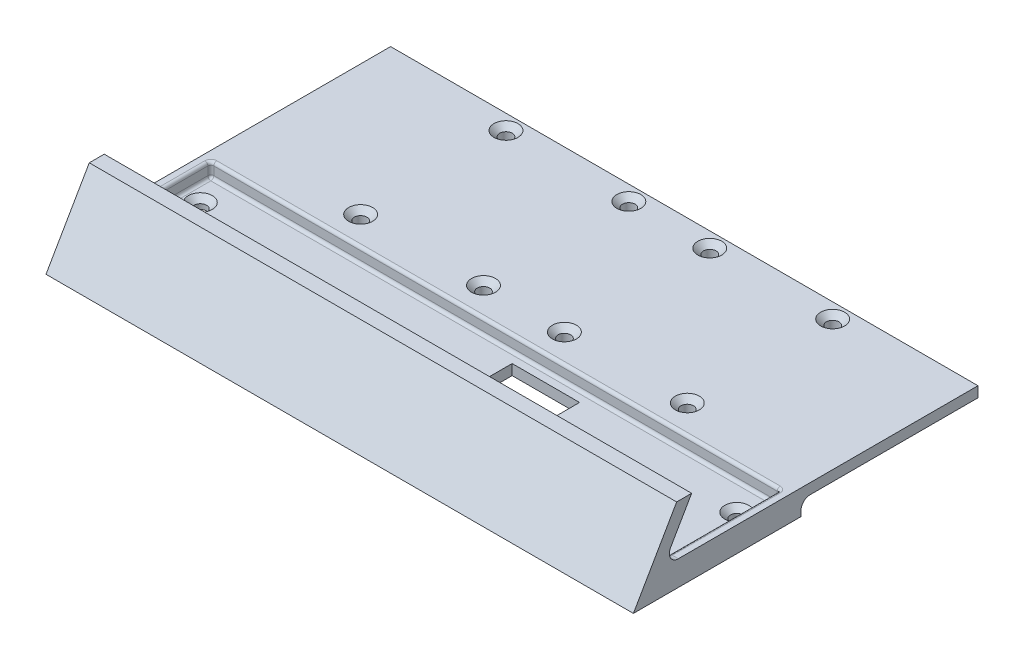
SolidWorks part; units mm, degrees
ref_plane "Alzado" through (0, 0, 0) normal (0, 0, 1) x (1, 0, 0)
ref_plane "Planta" through (0, 0, 0) normal (0, 1, 0) x (1, 0, 0)
ref_plane "Vista lateral" through (0, 0, 0) normal (1, 0, 0) x (0, 0, -1)
sketch "Sketch1" plane through (0, 0, 0) normal (1, 0, 0) x (0, 0, -1)
  line L0 (-13.9334, 0) -> (0.5004, 25)
  line L1 (-88.9489, -50.86) -> (38.0613, -50.86) construction
  line L2 (0.5004, 25) -> (5.5004, 25)
  line L3 (5.5004, 25) -> (-8.9334, 0)
  line L4 (-8.9334, 0) -> (-13.9334, 0)
  dimension "D1" = 120
  dimension "D2" = 25
  dimension "D3" = 5
  dimension "D4" = 5
extrude "Boss-Extrude1" add sketch "Sketch1" along normal blind 196
sketch "Sketch2" plane through (0, 0, 0) normal (1, 0, 0) x (0, 0, -1)
  line L0 (42.0107, 0) -> (42.0107, 4.8111)
  line L1 (101.0511, 0) -> (101.0511, -50.86) construction
  line L6 (-11.9127, 3.5) -> (-13.9334, 0)
  line L8 (-11.9127, 3.5) -> (38.0613, 3.5)
  line L9 (-13.9334, 0) -> (38.0613, 0)
  line L10 (42.0107, 4.8111) -> (101.0511, 4.8111)
  line L16 (101.0511, 4.8111) -> (101.0511, 8.3111)
  line L17 (101.0511, 8.3111) -> (38.0613, 8.3111)
  line L18 (38.0613, 8.3111) -> (38.0613, 3.5)
  line L19 (38.0613, 0) -> (42.0107, 0)
  point P9 (38.0613, 8.3111)
  point P12 (-13.9334, 0)
  point P13 (-11.9127, 3.5)
  dimension "D1" = 3.5
  dimension "D2" = 3.5
extrude "Boss-Extrude2" add sketch "Sketch2" along normal blind 196
sketch "Sketch3" plane through (0, 0, 0) normal (0, -1, 0) x (1, 0, 0)
  circle A0 centre (187.5, -29.0613) radius 1.585
  circle A1 centre (8.5, -29.0613) radius 1.585
  circle A2 centre (43.5, -47.5511) radius 1.585
  circle A3 centre (84.5, -47.5511) radius 1.585
  circle A4 centre (111.5, -47.5511) radius 1.585
  circle A5 centre (152.5, -47.5511) radius 1.585
  circle A6 centre (152.5, -96.0511) radius 1.585
  circle A7 centre (111.5, -96.0511) radius 1.585
  circle A8 centre (84.5, -96.0511) radius 1.585
  circle A9 centre (43.5, -96.0511) radius 1.585
extrude "Cut-Extrude2" cut sketch "Sketch3" against normal through all and the other way through all
hole_wizard "Avellanado para tornillo con cabeza avellanada en cruz de M3.52" positions "3DSketch2" profile "Sketch6" countersink size "M3.5" standard "AS"
sketch3d "3DSketch2"
  line L0 (152.5, 8.3111, -47.5511) -> (152.5, 4.8111, -47.5511) construction
  line L1 (187.5, 3.5, -29.0613) -> (187.5, 0, -29.0613) construction
  line L2 (111.5, 8.3111, -47.5511) -> (111.5, 4.8111, -47.5511) construction
  line L3 (111.5, 8.3111, -96.0511) -> (111.5, 4.8111, -96.0511) construction
  line L4 (152.5, 8.3111, -96.0511) -> (152.5, 4.8111, -96.0511) construction
  line L5 (84.5, 8.3111, -96.0511) -> (84.5, 4.8111, -96.0511) construction
  line L6 (84.5, 8.3111, -47.5511) -> (84.5, 4.8111, -47.5511) construction
  line L7 (43.5, 8.3111, -47.5511) -> (43.5, 4.8111, -47.5511) construction
  line L8 (43.5, 8.3111, -96.0511) -> (43.5, 4.8111, -96.0511) construction
  line L9 (8.5, 3.5, -29.0613) -> (8.5, 0, -29.0613) construction
  point P0 (152.5, 8.3111, -47.5511)
  point P4 (187.5, 3.5, -29.0613)
  point P8 (111.5, 8.3111, -47.5511)
  point P12 (111.5, 8.3111, -96.0511)
  point P16 (152.5, 8.3111, -96.0511)
  point P20 (84.5, 8.3111, -96.0511)
  point P24 (84.5, 8.3111, -47.5511)
  point P28 (43.5, 8.3111, -47.5511)
  point P32 (43.5, 8.3111, -96.0511)
  point P36 (8.5, 3.5, -29.0613)
sketch "Sketch6" plane through (152.5, 8.3111, -47.5511) normal (1, 0, 0) x (0, 0, 1)
  line L0 (0, 0) -> (0, 11.2618)
  line L1 (0, 11.2618) -> (2.1, 10)
  line L2 (2.1, 10) -> (2.1, 1.8348)
  line L3 (2.1, 1.8348) -> (4, 0)
  line L5 (4, 0) -> (0, 0)
  line L6 (-2.1, 1.8348) -> (-4, 0) construction
  line L10 (0, 11.2618) -> (-2.1, 10) construction
  line L11 (0, -6.35) -> (0, 107.95) construction
  dimension "Diámetro de taladro" = 4.2
  dimension "Profundidad de taladro" = 10
  dimension "Ángulo de avellanado cercano" = 8
  dimension "Ángulo de avellanado lejano" = 92
  dimension "Ángulo de perforador" = 118
sketch "Sketch8" plane through (0, 0, -42.0107) normal (0, 0, -1) x (-1, 0, 0)
  line L0 (-196, 0) -> (-196, 4.8111) construction
  line L1 (-158.5, -5.19) -> (-37.5, -5.19)
  line L2 (-158.5, -5.19) -> (-158.5, 6.4322)
  line L3 (-158.5, 6.4322) -> (-37.5, 6.4322)
  line L4 (-37.5, -5.19) -> (-37.5, 6.4322)
  line L5 (-158.5, -5.19) -> (-37.5, 6.4322) construction
  line L6 (-158.5, 6.4322) -> (-37.5, -5.19) construction
  line L7 (0, 0) -> (0, 4.8111) construction
  line L8 (-148.5, -5.19) -> (-115.5, -5.19) construction
  point P4 (-98.375, 2.4056)
  dimension "D1" = 37.5
  dimension "D2" = 37.5
extrude "Boss-Extrude3" add sketch "Sketch8" along normal up to vertex (59.0404 mm away) and the other way blind 2 up to point (0, 4.8111, -101.0511)
fillet "Fillet3" radius 3 6 edges at (158.5, 4.8111, -71.5309) (158.5, 2.4056, -42.0107) (177.25, 4.8111, -42.0107) (18.75, 4.8111, -42.0107) (37.5, 2.4056, -42.0107) (37.5, 4.8111, -71.5309)
sketch "Sketch9" plane through (0, 8.3111, 0) normal (0, 1, 0) x (1, 0, 0)
  circle A0 centre (43.5, 47.5511) radius 2.1
  circle A1 centre (84.5, 47.5511) radius 2.1
  circle A2 centre (152.5, 47.5511) radius 2.1
  circle A3 centre (152.5, 96.0511) radius 2.1
  circle A4 centre (111.5, 96.0511) radius 2.1
  circle A5 centre (111.5, 47.5511) radius 2.1
  circle A7 centre (84.5, 96.0511) radius 2.1
  circle A8 centre (43.5, 96.0511) radius 2.1
extrude "Cut-Extrude3" cut sketch "Sketch9" against normal up to next
sketch "Sketch10" plane through (0, 0, 0) normal (0, -1, 0) x (-1, 0, 0)
  line L1 (-67.6351, -5.9334) -> (-90.1351, -5.9334)
  line L2 (-67.6351, -5.9334) -> (-67.6351, 2.0666)
  line L3 (-67.6351, 2.0666) -> (-90.1351, 2.0666)
  line L4 (-90.1351, -5.9334) -> (-90.1351, 2.0666)
  line L5 (-67.6351, -5.9334) -> (-90.1351, 2.0666) construction
  line L6 (-67.6351, 2.0666) -> (-90.1351, -5.9334) construction
  line L7 (-107.0575, 22.5466) -> (-129.5575, 22.5466)
  line L8 (-107.0575, 22.5466) -> (-107.0575, 34.5466)
  line L9 (-107.0575, 34.5466) -> (-129.5575, 34.5466)
  line L10 (-129.5575, 22.5466) -> (-129.5575, 34.5466)
  line L11 (-107.0575, 22.5466) -> (-129.5575, 34.5466) construction
  line L12 (-107.0575, 34.5466) -> (-129.5575, 22.5466) construction
  point P4 (-78.8851, -1.9334)
  point P9 (-118.3075, 28.5466)
extrude "Cut-Extrude4" cut sketch "Sketch10" against normal blind 4
fillet "Fillet4" radius 5 1 edges at (78.8851, 3.5, -2.0666)
sketch "Sketch11" plane through (0, 0, 0) normal (1, 0, 0) x (0, 0, -1)
  line L1 (40.0605, 8.3111) -> (-8.2744, 8.3111)
  line L2 (40.0605, 8.3111) -> (40.0605, 1.9288)
  line L3 (40.0605, 1.9288) -> (-8.2744, 1.9288)
  line L4 (-8.2744, 8.3111) -> (-8.2744, 1.9288)
  line L5 (40.0605, 8.3111) -> (-8.2744, 1.9288) construction
  line L6 (40.0605, 1.9288) -> (-8.2744, 8.3111) construction
  point P4 (15.893, 5.12)
extrude "Boss-Extrude4" add sketch "Sketch11" along normal blind 3
ref_plane "Plane2" through (98, 0, 0) normal (-1, 0, 0) x (0, 0, 1)
mirror "Mirror1" about plane through (98, 0, 0) normal (-1, 0, 0) of "Boss-Extrude4"
fillet "Fillet5" radius 1 8 edges at (3, 5.9056, -38.0613) (193, 5.9056, -38.0613) (98, 3.5, -38.0613) (193, 3.5, -15.5743) (3, 3.5, -15.5743) (3, 5.9056, 5.5238) (98, 3.5, 6.9127) (193, 5.9056, 5.5238)
fillet "Fillet6" radius 3 2 edges at (2, 8.3111, 4.135) (194, 8.3111, 4.135)
fillet "Fillet7" radius 1 9 edges at (192.6599, 11.6512, 1.9195) (193, 8.8812, 0.6981) (193, 8.3111, -19.0612) (192.7071, 8.3111, -37.7684) (3.3401, 11.6512, 1.9195) (3, 8.8812, 0.6981) (3, 8.3111, -19.0612) (3.2929, 8.3111, -37.7684) (98, 8.3111, -38.0613)
fillet "Fillet8" radius 1.75 1 edges at (98, 0, -40.0107)
